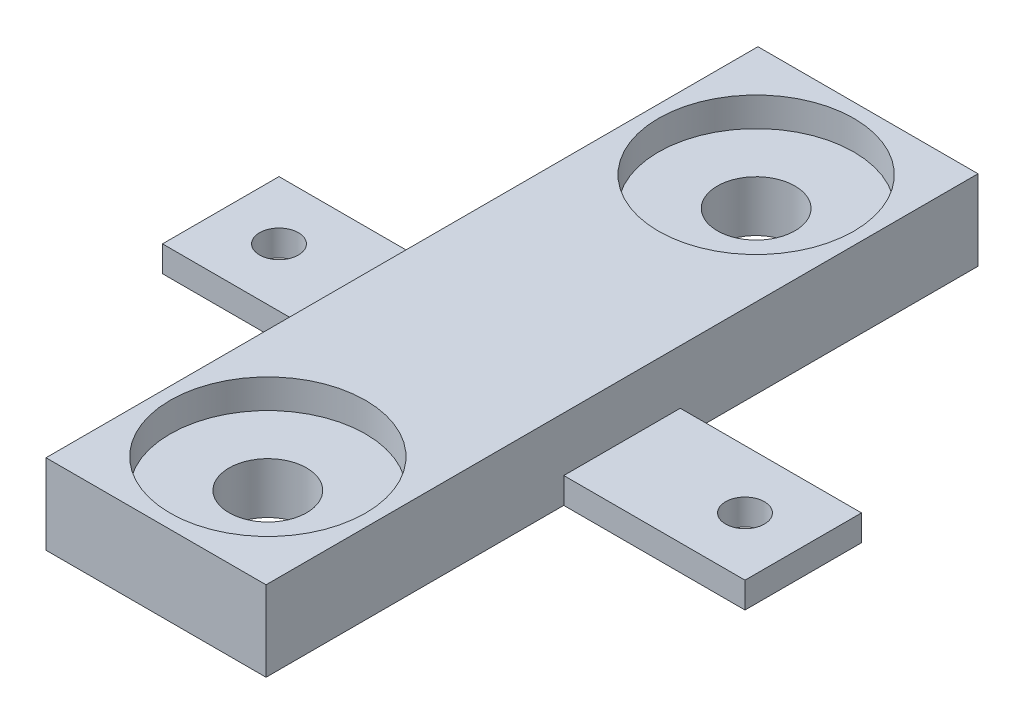
SolidWorks part; units mm, degrees
material "Nylon 101"
ref_plane "Front Plane" through (0, 0, 0) normal (0, 0, 1) x (1, 0, 0)
ref_plane "Top Plane" through (0, 0, 0) normal (0, 1, 0) x (1, 0, 0)
ref_plane "Right Plane" through (0, 0, 0) normal (1, 0, 0) x (0, 0, -1)
sketch "Sketch1" plane through (0, 0, 0) normal (0, 1, 0) x (1, 0, 0)
  line L0 (0, -18.8625) -> (0, -27.5) construction
  line L1 (-8.5, 27.5) -> (8.5, 27.5)
  line L2 (-8.5, 27.5) -> (-8.5, -27.5)
  line L3 (-8.5, -27.5) -> (8.5, -27.5)
  line L4 (8.5, 27.5) -> (8.5, -27.5)
  line L5 (-8.5, 0) -> (0, 0) construction
  line L6 (0, 18.8625) -> (0, -18.8625) construction
  line L7 (-18, 0) -> (18, 0) construction
  line L8 (-8.5, 4.5) -> (-22.5, 4.5)
  line L9 (-8.5, 4.5) -> (-8.5, -4.5)
  line L10 (-8.5, -4.5) -> (-22.5, -4.5)
  line L11 (-22.5, 4.5) -> (-22.5, -4.5)
  line L12 (8.5, 4.5) -> (22.5, 4.5)
  line L13 (8.5, 4.5) -> (8.5, -4.5)
  line L14 (8.5, -4.5) -> (22.5, -4.5)
  line L15 (22.5, 4.5) -> (22.5, -4.5)
  circle A0 centre (0, 18.8625) radius 7.55
  circle A1 centre (0, -18.8625) radius 7.55
  circle A2 centre (-18, 0) radius 1.5
  circle A3 centre (18, 0) radius 1.5
  point P24 (0, 0)
  point P26 (0, 0)
  point P28 (-22.5, 0)
  dimension "D3" = 15.1
  dimension "D7" = 3
  dimension "D1" = 55
  dimension "D2" = 17
  dimension "D4" = 37.725
  dimension "D6" = 36
  dimension "D8" = 4.5
  dimension "D9" = 9
extrude "Boss-Extrude1" add sketch "Sketch1" along normal blind 2 contours L4 L1 L2 L3 A1 A0 | L15 L12 L4 L14 A3 | L8 L11 L10 L2 A2 | A1 | A0 region at (0, 0, 0) region at (-15.3514, 0, 0) region at (15.3514, 0, 0) region at (0, 0, -18.8625) region at (0, 0, 18.8625)
extrude "Boss-Extrude2" add sketch "Sketch1<4>" along normal blind 1.94 from surface contours L4 L1 L2 L3 A1 A0 | A1 | A0 region at (0, 0, 0) region at (0, 0, -18.8625) region at (0, 0, 18.8625) starting at face at (0, 2, 0)
sketch "Sketch1<4>" plane through (0, 0, 0) normal (0, 1, 0) x (1, 0, 0) same geometry as "Sketch1"
extrude "Boss-Extrude3" add sketch "Sketch1<5>" along normal blind 2.25 from surface contours L4 L1 L2 L3 A1 A0 region at (0, 0, 0) starting at face at (0, 3.94, 0)
sketch "Sketch1<5>" plane through (0, 0, 0) normal (0, 1, 0) x (1, 0, 0) same geometry as "Sketch1"
sketch "Sketch3" plane through (0, 0, 0) normal (0, -1, 0) x (1, 0, 0)
  circle A0 centre (0, -18.8625) radius 3
  circle A1 centre (0, 18.8625) radius 3
  circle A2 centre (0, 18.8625) radius 7.55 construction
  dimension "D1" = 6
extrude "Cut-Extrude1" cut sketch "Sketch3" against normal through all
equation "\"D1@Boss-Extrude2\"= \"base_thickness\" - 2.25mm - 1.5mm"
equation "\"bottomThickness\"= .220in"
equation "\"wallThickness\"= .125in"
equation "\"wall_thickness\" = 2.75mm"
equation "\"base_thickness\" = 5.69mm"
